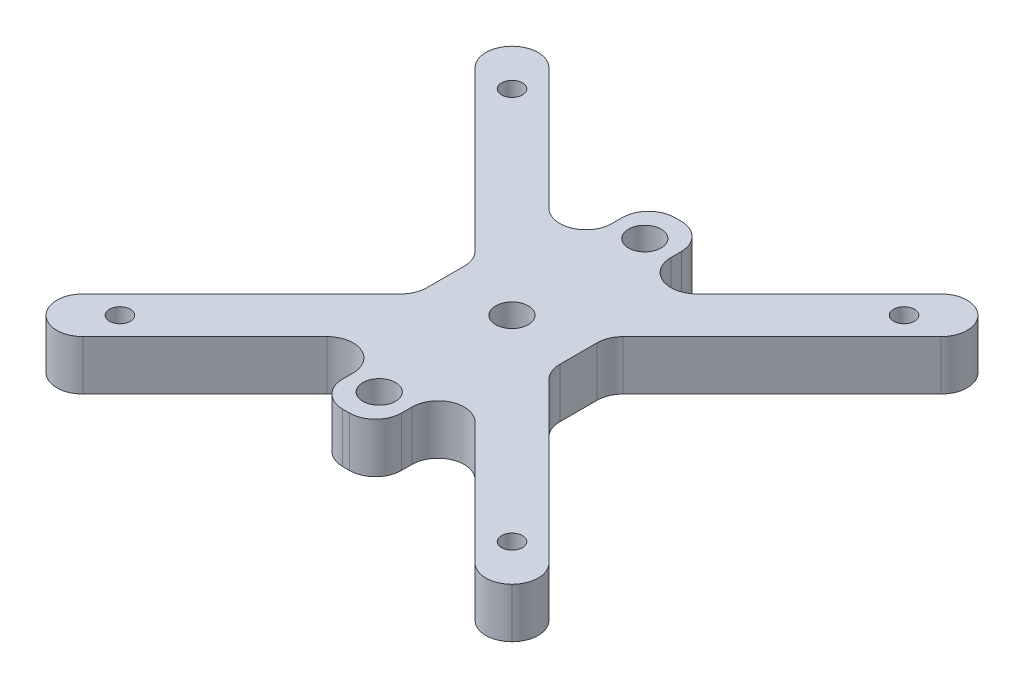
SolidWorks part; units mm, degrees
ref_plane "Front Plane" through (0, 0, 0) normal (0, 0, 1) x (1, 0, 0)
ref_plane "Top Plane" through (0, 0, 0) normal (0, 1, 0) x (1, 0, 0)
ref_plane "Right Plane" through (0, 0, 0) normal (1, 0, 0) x (0, 0, -1)
sketch "Sketch1" plane through (0, 0, 0) normal (0, 1, 0) x (1, 0, 0)
  line L4 (-37.5, -37.5) -> (37.5, 37.5) construction
  line L5 (37.5, -37.5) -> (-37.5, 37.5) construction
  line L6 (-37.5, 37.5) -> (37.5, 37.5) construction
  line L7 (-12.7, 5.6289) -> (-48.1066, 41.0355)
  line L8 (-48.1066, 41.0355) -> (-41.0355, 48.1066)
  line L10 (-5.6289, 12.7) -> (5.6289, 12.7) construction
  line L11 (5.6289, 12.7) -> (41.0355, 48.1066)
  line L12 (41.0355, 48.1066) -> (48.1066, 41.0355)
  line L13 (48.1066, 41.0355) -> (12.7, 5.6289)
  line L14 (12.7, 5.6289) -> (12.7, -5.6289)
  line L15 (12.7, -5.6289) -> (48.1066, -41.0355)
  line L16 (48.1066, -41.0355) -> (41.0355, -48.1066)
  line L17 (41.0355, -48.1066) -> (5.6289, -12.7)
  line L18 (5.6289, -12.7) -> (-5.6289, -12.7) construction
  line L19 (-5.6289, -12.7) -> (-41.0355, -48.1066)
  line L20 (-41.0355, -48.1066) -> (-48.1066, -41.0355)
  line L21 (-48.1066, -41.0355) -> (-12.7, -5.6289)
  line L22 (-12.7, -5.6289) -> (-12.7, 5.6289)
  line L23 (0, 12.7) -> (0, -12.7) construction
  line L24 (-41.0355, 48.1066) -> (-5.6289, 12.7)
  line L25 (37.5, 37.5) -> (44.5711, 44.5711) construction
  line L26 (37.5, -37.5) -> (44.5711, -44.5711) construction
  line L27 (-37.5, -37.5) -> (-44.5711, -44.5711) construction
  line L28 (-37.5, 37.5) -> (-44.5711, 44.5711) construction
  line L29 (-37.5, -37.5) -> (37.5, -37.5) construction
  line L30 (-5.6289, -12.7) -> (5.6289, -12.7) construction
  line L31 (-5.6289, -12.7) -> (-5.6289, -31.75)
  line L32 (5.6289, -12.7) -> (5.6289, -31.75)
  line L33 (-5.6289, -31.75) -> (5.6289, -31.75)
  line L34 (-5.6289, 12.7) -> (5.6289, 12.7) construction
  line L35 (-5.6289, 12.7) -> (-5.6289, 31.75)
  line L36 (5.6289, 12.7) -> (5.6289, 31.75)
  line L37 (-5.6289, 31.75) -> (5.6289, 31.75)
  circle A0 centre (37.5, 37.5) radius 2
  circle A1 centre (37.5, -37.5) radius 2
  circle A2 centre (-37.5, -37.5) radius 2
  circle A3 centre (-37.5, 37.5) radius 2
  circle A4 centre (0, 0) radius 3.125
  circle A5 centre (0, 25.4) radius 3.125
  circle A6 centre (0, -25.4) radius 3.125
  point P1 (0, 0)
  point P28 (0, 0)
  dimension "D2" = 4
  dimension "D6" = 6.25
  dimension "D1" = 75
  dimension "D3" = 25.4
  dimension "D4" = 10
  dimension "D5" = 10
  dimension "D7" = 25.4
  dimension "D8" = 25.4
  dimension "D9" = 25.4
  dimension "D10" = 19.05
extrude "Boss-Extrude1" add sketch "Sketch1" along normal blind 9.525
fillet "Fillet1" radius 5 20 edges at (12.7, 4.7625, -5.6289) (12.7, 4.7625, 5.6289) (48.1066, 4.7625, 41.0355) (41.0355, 4.7625, 48.1066) (-41.0355, 4.7625, 48.1066) (-48.1066, 4.7625, 41.0355) (-12.7, 4.7625, 5.6289) (-48.1066, 4.7625, -41.0355) (-41.0355, 4.7625, -48.1066) (41.0355, 4.7625, -48.1066) (48.1066, 4.7625, -41.0355) (-12.7, 4.7625, -5.6289) (-5.6289, 4.7625, 31.75) (-5.6289, 4.7625, 12.7) (5.6289, 4.7625, 12.7) (5.6289, 4.7625, -12.7) (5.6289, 4.7625, -31.75) (-5.6289, 4.7625, -31.75) (-5.6289, 4.7625, -12.7) (5.6289, 4.7625, 31.75)
